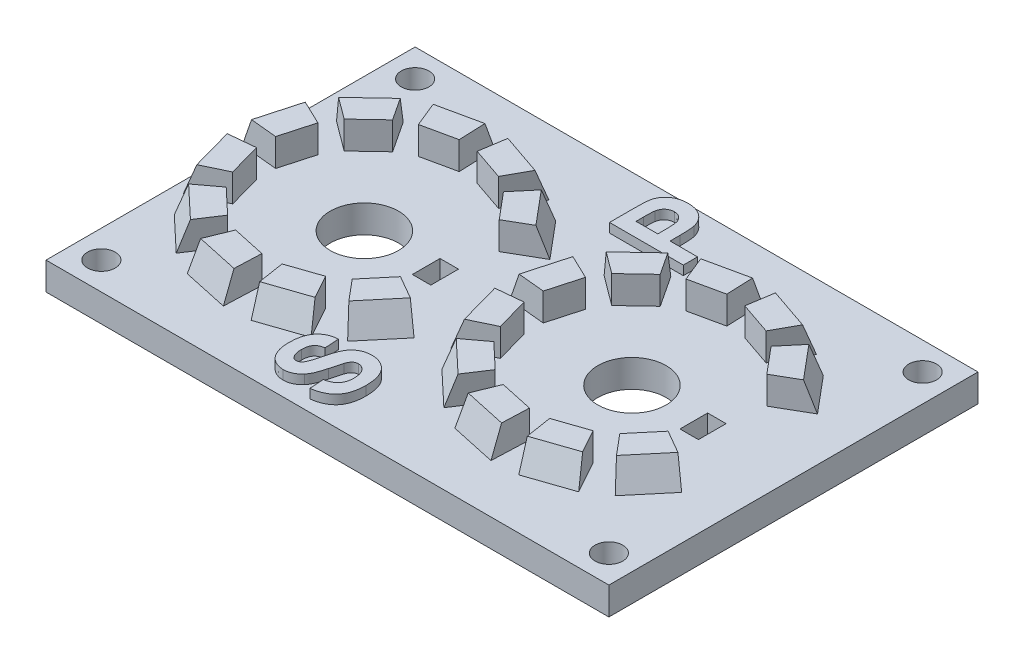
SolidWorks part; units mm, degrees
ref_plane "Спереди" through (0, 0, 0) normal (0, 0, 1) x (1, 0, 0)
ref_plane "Сверху" through (0, 0, 0) normal (0, 1, 0) x (1, 0, 0)
ref_plane "Справа" through (0, 0, 0) normal (1, 0, 0) x (0, 0, -1)
sketch "Sketch1" plane through (0, 0, 0) normal (0, 1, 0) x (1, 0, 0)
  line L0 (35, 20) -> (35, 7)
  line L1 (35, -20) -> (-35, -20)
  line L2 (35, -20) -> (35, 20) construction
  line L3 (35, 20) -> (-35, 20)
  line L4 (-35, -20) -> (-35, 20)
  line L5 (35, -20) -> (-35, 20) construction
  line L6 (35, 20) -> (-35, -20) construction
  line L7 (35, -7) -> (35, -20)
  arc A0 (35, 7) -> (35, -7) centre (35, 0) ccw
  point P0 (0, 0)
  dimension "D3" = 7
  dimension "D1" = 70
  dimension "D2" = 40
extrude "Boss-Extrude1" add sketch "Sketch1" along normal blind 20
sketch "Sketch2" plane through (0, 20, 0) normal (0, 1, 0) x (1, 0, 0)
  line L0 (-30.2502, 0) -> (28, 0) construction
  line L1 (-35, 20) -> (-35, -20) construction
  line L2 (23, -17) -> (-32, -17)
  line L3 (23, -17) -> (23, 17)
  line L4 (23, 17) -> (-32, 17)
  line L5 (-32, -17) -> (-32, 17)
  line L6 (23, -17) -> (-32, 17) construction
  line L7 (23, 17) -> (-32, -17) construction
  line L8 (35, 20) -> (-35, 20) construction
  arc A0 (35, 7) -> (35, -7) centre (35, 0) ccw construction
  point P5 (-4.5, 0)
  dimension "D1" = 3
  dimension "D2" = 3
  dimension "D3" = 55
extrude "Cut-Extrude1" cut sketch "Sketch2" against normal offset from surface (17 mm away) 3 up to face at (10.5, 0, 0)
sketch "Sketch6" plane through (0, 20, 0) normal (0, 1, 0) x (1, 0, 0)
  line L0 (23, 17) -> (-32, 17) construction
  line L1 (-32, 17) -> (-32, -17) construction
  line L2 (-32, -17) -> (23, -17) construction
  line L3 (23, -17) -> (23, 17) construction
  line L4 (-32, -14) -> (-32, -17)
  line L5 (-32, -17) -> (-29, -17)
  line L6 (23, -14) -> (23, -17)
  line L7 (23, -17) -> (20, -17)
  line L8 (20, 17) -> (23, 17)
  line L9 (23, 17) -> (23, 14)
  line L10 (-32, 14) -> (-32, 17)
  line L12 (-32, 17) -> (-29, 17)
  arc A0 (-29, 17) -> (-32, 14) centre (-32, 17) cw
  arc A1 (-32, -14) -> (-29, -17) centre (-32, -17) cw
  arc A2 (20, -17) -> (23, -14) centre (23, -17) cw
  arc A3 (23, 14) -> (20, 17) centre (23, 17) cw
  dimension "D1" = 3
extrude "Boss-Extrude3" add sketch "Sketch6" against normal up to next
sketch "Sketch7" plane through (0, 20, 0) normal (0, 1, 0) x (1, 0, 0)
  circle A0 centre (-32, 17) radius 1.5
  circle A1 centre (23, 17) radius 1.5
  circle A2 centre (23, -17) radius 1.5
  circle A3 centre (-32, -17) radius 1.5
  dimension "D1" = 3
extrude "Cut-Extrude4" cut sketch "Sketch7" against normal through all
sketch "Sketch8" plane through (35, 0, 0) normal (1, 0, 0) x (0, 0, -1)
  circle A0 centre (0, 0) radius 43.9747
extrude "Cut-Extrude5" cut sketch "Sketch8" against normal offset from surface (9 mm away) 3 up to face at (23, 11.5, 0)
sketch "Sketch10" plane through (0, 20, 0) normal (0, 1, 0) x (1, 0, 0)
  circle A0 centre (0, 0) radius 55.9266
extrude "Cut-Extrude6" cut sketch "Sketch10" against normal up to surface (17 mm away) up to face at (-4.5, 3, 0)
sketch "Sketch11" plane through (0, 3, 0) normal (0, 1, 0) x (1, 0, 0)
  line L0 (-35, 0) -> (26, 0) construction
  line L1 (-35, 20) -> (-35, -20) construction
  line L2 (26, 20) -> (26, -20) construction
  line L3 (-29, 0) -> (-29, 11.5) construction
  line L4 (-29, 11.5) -> (-12, 11.5) construction
  line L5 (-12, 11.5) -> (-12, 0) construction
  line L6 (-20.5, 11.5) -> (-20.5, -8.5) construction
  line L7 (-16.8, 0) -> (-12.8, 0) construction
  line L8 (-13.8, -1.5) -> (-11.8, -1.5)
  line L9 (-13.8, -1.5) -> (-13.8, 1.5)
  line L10 (-13.8, 1.5) -> (-11.8, 1.5)
  line L11 (-11.8, -1.5) -> (-11.8, 1.5)
  line L12 (-13.8, -1.5) -> (-11.8, 1.5) construction
  line L13 (-13.8, 1.5) -> (-11.8, -1.5) construction
  line L14 (0, 0) -> (0, 11.5) construction
  line L15 (0, 11.5) -> (17, 11.5) construction
  line L16 (17, 11.5) -> (17, 0) construction
  line L17 (8.5, 11.5) -> (8.5, -8.5) construction
  line L18 (12.2, 0) -> (16.2, 0) construction
  line L19 (15.2, -1.5) -> (17.2, -1.5)
  line L20 (15.2, -1.5) -> (15.2, 1.5)
  line L21 (15.2, 1.5) -> (17.2, 1.5)
  line L22 (17.2, -1.5) -> (17.2, 1.5)
  line L23 (15.2, -1.5) -> (17.2, 1.5) construction
  line L24 (15.2, 1.5) -> (17.2, -1.5) construction
  circle A0 centre (8.5, 0) radius 3.7
  circle A1 centre (8.5, 0) radius 8.5 construction
  circle A2 centre (-20.5, 0) radius 3.7
  circle A3 centre (-20.5, 0) radius 8.5 construction
  dimension "D1" = 3
  dimension "D7" = 7.4
  dimension "D8" = 7.4
  dimension "D9" = 17
  dimension "D2" = 20
  dimension "D3" = 3
  dimension "D4" = 11.5
  dimension "D5" = 4
  dimension "D6" = 4
  dimension "D10" = 6
  dimension "D11" = 12
extrude "Cut-Extrude7" cut sketch "Sketch11" against normal through all
sketch "Sketch13" plane through (0, 3, 0) normal (0, 1, 0) x (1, 0, 0)
  line L0 (-20.5, 0) -> (-8.8087, -6.75) construction
  line L1 (-20.5, 0) -> (-8.8087, 6.75) construction
  line L2 (-8.8087, -6.75) -> (-8.8087, 6.75) construction
  line L4 (26, 20) -> (26, -20) construction
  line L5 (8.5, 0) -> (20.1913, -6.75) construction
  line L6 (20.1913, -6.75) -> (20.1913, 6.75) construction
  line L7 (20.1913, 6.75) -> (8.5, 0) construction
  line L8 (20.1913, -6.75) -> (17.7665, -5.35)
  line L9 (17.7665, -5.35) -> (15.3778, -8.1967)
  line L10 (15.3778, -8.1967) -> (17.1776, -10.3416)
  line L11 (17.1776, -10.3416) -> (20.1913, -6.75)
  line L12 (8.5, 0) -> (17.1776, -10.3416) construction
  line L13 (10.1534, -10.5715) -> (10.586, -13.3379)
  line L14 (13.6693, -9.3685) -> (10.1534, -10.5715)
  line L15 (15.022, -11.82) -> (13.6693, -9.3685)
  line L16 (10.586, -13.3379) -> (15.022, -11.82)
  line L17 (4.4533, -9.9052) -> (3.3943, -12.4973)
  line L18 (8.0851, -10.692) -> (4.4533, -9.9052)
  line L19 (7.9765, -13.4898) -> (8.0851, -10.692)
  line L20 (3.3943, -12.4973) -> (7.9765, -13.4898)
  line L21 (-0.0827, -6.3896) -> (-2.3287, -8.0616)
  line L22 (2.6203, -8.9397) -> (-0.0827, -6.3896)
  line L23 (1.0816, -11.2791) -> (2.6203, -8.9397)
  line L24 (-2.3287, -8.0616) -> (1.0816, -11.2791)
  line L25 (-2.1497, -1.0359) -> (-4.9366, -1.3069)
  line L26 (-1.1532, -4.6158) -> (-2.1497, -1.0359)
  line L27 (-3.6793, -5.8237) -> (-1.1532, -4.6158)
  line L28 (-4.9366, -1.3069) -> (-3.6793, -5.8237)
  line L29 (-1.1532, 4.6158) -> (-3.6793, 5.8237)
  line L30 (-2.1497, 1.0359) -> (-1.1532, 4.6158)
  line L31 (-4.9366, 1.3069) -> (-2.1497, 1.0359)
  line L32 (-3.6793, 5.8237) -> (-4.9366, 1.3069)
  line L33 (2.6203, 8.9397) -> (1.0816, 11.2791)
  line L34 (-0.0827, 6.3896) -> (2.6203, 8.9397)
  line L35 (-2.3287, 8.0616) -> (-0.0827, 6.3896)
  line L36 (1.0816, 11.2791) -> (-2.3287, 8.0616)
  line L37 (8.0851, 10.692) -> (7.9765, 13.4898)
  line L38 (4.4533, 9.9052) -> (8.0851, 10.692)
  line L39 (3.3943, 12.4973) -> (4.4533, 9.9052)
  line L40 (7.9765, 13.4898) -> (3.3943, 12.4973)
  line L41 (13.6693, 9.3685) -> (15.022, 11.82)
  line L42 (10.1534, 10.5715) -> (13.6693, 9.3685)
  line L43 (10.586, 13.3379) -> (10.1534, 10.5715)
  line L44 (15.022, 11.82) -> (10.586, 13.3379)
  line L45 (17.7665, 5.35) -> (20.1913, 6.75)
  line L46 (15.3778, 8.1967) -> (17.7665, 5.35)
  line L47 (17.1776, 10.3416) -> (15.3778, 8.1967)
  line L48 (20.1913, 6.75) -> (17.1776, 10.3416)
  line L49 (-20.5, 0) -> (-11.8224, -10.3416) construction
  line L50 (-11.8224, -10.3416) -> (-8.8087, -6.75) construction
  line L51 (-13.6222, -8.1967) -> (-11.8224, -10.3416)
  line L52 (-11.8224, -10.3416) -> (-8.8087, -6.75)
  line L53 (-8.8087, -6.75) -> (-11.2335, -5.35)
  line L54 (-11.2335, -5.35) -> (-13.6222, -8.1967)
  line L55 (-15.3307, -9.3685) -> (-18.8466, -10.5715)
  line L56 (-13.978, -11.82) -> (-15.3307, -9.3685)
  line L57 (-18.414, -13.3379) -> (-13.978, -11.82)
  line L58 (-18.8466, -10.5715) -> (-18.414, -13.3379)
  line L59 (-20.9149, -10.692) -> (-24.5467, -9.9052)
  line L60 (-21.0235, -13.4898) -> (-20.9149, -10.692)
  line L61 (-25.6057, -12.4973) -> (-21.0235, -13.4898)
  line L62 (-24.5467, -9.9052) -> (-25.6057, -12.4973)
  line L63 (-26.3797, -8.9397) -> (-29.0827, -6.3896)
  line L64 (-27.9184, -11.2791) -> (-26.3797, -8.9397)
  line L65 (-31.3287, -8.0616) -> (-27.9184, -11.2791)
  line L66 (-29.0827, -6.3896) -> (-31.3287, -8.0616)
  line L67 (-30.1532, -4.6158) -> (-31.1497, -1.0359)
  line L68 (-32.6793, -5.8237) -> (-30.1532, -4.6158)
  line L69 (-33.9366, -1.3069) -> (-32.6793, -5.8237)
  line L70 (-31.1497, -1.0359) -> (-33.9366, -1.3069)
  line L71 (-31.1497, 1.0359) -> (-30.1532, 4.6158)
  line L72 (-33.9366, 1.3069) -> (-31.1497, 1.0359)
  line L73 (-32.6793, 5.8237) -> (-33.9366, 1.3069)
  line L74 (-30.1532, 4.6158) -> (-32.6793, 5.8237)
  line L75 (-29.0827, 6.3896) -> (-26.3797, 8.9397)
  line L76 (-31.3287, 8.0616) -> (-29.0827, 6.3896)
  line L77 (-27.9184, 11.2791) -> (-31.3287, 8.0616)
  line L78 (-26.3797, 8.9397) -> (-27.9184, 11.2791)
  line L79 (-24.5467, 9.9052) -> (-20.9149, 10.692)
  line L80 (-25.6057, 12.4973) -> (-24.5467, 9.9052)
  line L81 (-21.0235, 13.4898) -> (-25.6057, 12.4973)
  line L82 (-20.9149, 10.692) -> (-21.0235, 13.4898)
  line L83 (-18.8466, 10.5715) -> (-15.3307, 9.3685)
  line L84 (-18.414, 13.3379) -> (-18.8466, 10.5715)
  line L85 (-13.978, 11.82) -> (-18.414, 13.3379)
  line L86 (-15.3307, 9.3685) -> (-13.978, 11.82)
  line L87 (-13.6222, 8.1967) -> (-11.2335, 5.35)
  line L88 (-11.8224, 10.3416) -> (-13.6222, 8.1967)
  line L89 (-8.8087, 6.75) -> (-11.8224, 10.3416)
  line L90 (-11.2335, 5.35) -> (-8.8087, 6.75)
  circle A0 centre (-20.5, 0) radius 10.7 construction
  circle A1 centre (8.5, 0) radius 10.7 construction
  circle A2 centre (-20.5, 0) radius 13.5 construction
  circle A3 centre (8.5, 0) radius 13.5 construction
  circle A4 centre (8.5, 0) radius 10.7 construction
  circle A5 centre (8.5, 0) radius 10.7 construction
  circle A6 centre (8.5, 0) radius 10.7 construction
  circle A7 centre (8.5, 0) radius 10.7 construction
  circle A8 centre (8.5, 0) radius 10.7 construction
  circle A9 centre (8.5, 0) radius 10.7 construction
  circle A10 centre (8.5, 0) radius 10.7 construction
  circle A11 centre (8.5, 0) radius 10.7 construction
  circle A12 centre (8.5, 0) radius 10.7 construction
  point P64 (8.5, 0)
  point P66 (-21.4359, 0.2944)
  point P105 (-20.5, 0)
  dimension "D1" = 21.4
  dimension "D2" = 27
  dimension "D3" = 300
  dimension "D4" = 300
  dimension "D5" = 20
  dimension "D6" = 10
  dimension "D7" = 10
extrude "Boss-Extrude4" add sketch "Sketch13" along normal blind 3
chamfer "Chamfer1" distance 1.2 angle 70 20 edges at (18.6845, 3, -8.5458) (12.804, 3, -12.5789) (5.6854, 3, -12.9936) (-0.6235, 3, -9.6704) (-4.3079, 3, -3.5653) (-4.3079, 3, 3.5653) (-0.6235, 3, 9.6704) (5.6854, 3, 12.9936) (12.804, 3, 12.5789) (18.6845, 3, 8.5458) (-10.3155, 3, -8.5458) (-16.196, 3, -12.5789) (-23.3146, 3, -12.9936) (-29.6235, 3, -9.6704) (-33.3079, 3, -3.5653) (-33.3079, 3, 3.5653) (-29.6235, 3, 9.6704) (-23.3146, 3, 12.9936) (-16.196, 3, 12.5789) (-10.3155, 3, 8.5458) first distance on face at (-20.5, 3, 3.7)
sketch "Sketch14" plane through (0, 3, 0) normal (0, 1, 0) x (1, 0, 0)
  line L0 (-5, -20) -> (-5, 20) construction
  line L1 (-35, -20) -> (26, -20) construction
  line L2 (26, 20) -> (-35, 20) construction
  line L3 (-35, 20) -> (-35, 1.9615) construction
  line L4 (1, -20) -> (1, 20) construction
  line L5 (26, 20) -> (26, -20) construction
  text T0 "<b> S</b>" font "Arial" height 8
  text T1 "<b>          P</b>" font "Arial" height 8
  dimension "D1" = 30
  dimension "D2" = 25
extrude "Boss-Extrude5" add sketch "Sketch14" along normal blind 1
